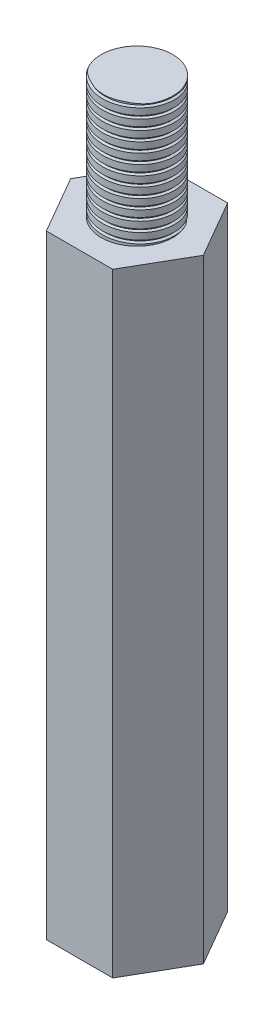
SolidWorks part; units mm, degrees
note: The reader was unsure of these and kept them because the rebuilt part matched: shared geometry of "草图1<3>".
ref_plane "前视基准面" through (0, 0, 0) normal (0, 0, 1) x (1, 0, 0)
ref_plane "上视基准面" through (0, 0, 0) normal (0, 1, 0) x (1, 0, 0)
ref_plane "右视基准面" through (0, 0, 0) normal (1, 0, 0) x (0, 0, -1)
sketch "草图1" plane through (0, 0, 0) normal (0, 1, 0) x (1, 0, 0)
  line L0 (0, 0) -> (0, 4.5761) construction
  line L1 (1.351, -2.34) -> (2.702, 0)
  line L2 (2.702, 0) -> (1.351, 2.34)
  line L3 (1.351, 2.34) -> (-1.351, 2.34)
  line L4 (-1.351, 2.34) -> (-2.702, 0)
  line L5 (-2.702, 0) -> (-1.351, -2.34)
  line L6 (-1.351, -2.34) -> (1.351, -2.34)
  line L7 (0, 4.5761) -> (0, -3.6794) construction
  circle A0 centre (0, 0) radius 2.34 construction
  circle A1 centre (0, 0) radius 1.46
  dimension "D1" = 4.68
  dimension "D2" = 2.92
extrude "凸台-拉伸1" add sketch "草图1" along normal blind 25 contours A1 | L5 L6 L1 L2 L3 L4 A1
extrude "切除-拉伸1" cut sketch "草图1<3>" along normal blind 5 contours A1
sketch "草图1<3>" plane through (0, 0, 0) normal (0, 1, 0) x (1, 0, 0) same geometry as "草图1"
sketch "草图2" plane through (0, 25, 0) normal (0, 1, 0) x (1, 0, 0)
  circle A0 centre (0, 0) radius 1.46
  dimension "D1" = 2.92
extrude "凸台-拉伸2" add sketch "草图2" along normal blind 5 separate body
ref_plane "基准面1" through (0, 0, 0) normal (0, 0, -1) x (-1, 0, 0)
sketch "草图4" plane through (0, 0, 0) normal (0, 0, -1) x (-1, 0, 0)
  line L0 (0, 0) -> (0, 28.5702) construction
  line L1 (-1.56, 25) -> (-1.56, 25.2)
  line L2 (-1.56, 25.2) -> (-1.36, 25.1333)
  line L3 (-1.36, 25.0667) -> (-1.56, 25)
  line L4 (-1.26, 25.1) -> (-2.0659, 25.1) construction
  line L5 (-2.0659, 25.1) -> (-0.8933, 25.1) construction
  line L7 (-1.46, 30) -> (-1.46, 25) construction
  line L8 (-1.36, 25.1333) -> (-1.36, 25.0667)
  line L9 (-1.46, 25) -> (1.46, 25) construction
  point P14 (0, 0)
  point P15 (0, 0)
  dimension "D1" = 0.1
  dimension "D2" = 0.1
  dimension "D3" = 0.1
  dimension "D4" = 0.3
  dimension "D5" = 0.2
  dimension "D6" = 0.1
  dimension "D7" = 0.0667
  dimension "D8" = 0.0667
ref_plane "基准面2" through (0, 25.1, 0) normal (0, 1, 0) x (1, 0, 0)
sketch "草图5" plane through (0, 25.1, 0) normal (0, 1, 0) x (1, 0, 0)
  circle A0 centre (0, 0) radius 1.46
  dimension "D1" = 2.92
curve "螺旋线/涡状线1" pitch 0.4 height 7.5 turns 18.75
sweep "切除-扫描1" cut profiles "草图4" path "螺旋线/涡状线1"
sketch "草图6" plane through (0, 0, 0) normal (0, -1, 0) x (1, 0, 0)
  circle A0 centre (0, 0) radius 1.46
curve "螺旋线/涡状线2" pitch 0.4 height 9.5 turns 23.75
sketch "草图7" plane through (0, 0, 0) normal (0, 0, -1) x (-1, 0, 0)
  line L0 (1.46, 0.2) -> (1.66, 0.1333)
  line L1 (1.66, 0.0667) -> (1.46, 0)
  line L2 (1.46, 0.2) -> (1.46, 0)
  line L3 (1.66, 0.1333) -> (1.66, 0.0667)
  line L8 (1.351, 0) -> (-1.351, 0) construction
  dimension "D1" = 0.2
  dimension "D3" = 1.46
  dimension "D4" = 0.2
sweep "切除-扫描2" cut profiles "草图7" path "螺旋线/涡状线2"
equation "\"chang\"= 20mm"
equation "\"r\"= 2.92mm"
equation "\"luowengao\"= 6.5mm"
equation "\"rr\"= 4.68mm"
equation "\"D1@草图1\"=\"rr\""
equation "\"D2@草图1\"=\"r\""
equation "\"D1@凸台-拉伸1\"=\"chang\""
equation "\"D1@切除-拉伸1\"=\"luowengao\"+5mm"
equation "\"D1@草图2\"=\"r\""
equation "\"D1@凸台-拉伸2\"=\"luowengao\""
